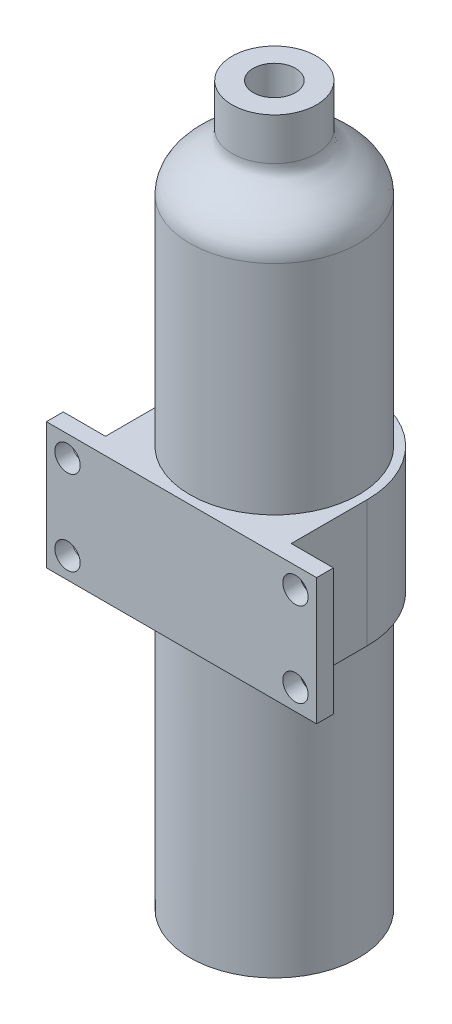
SolidWorks part; units mm, degrees
ref_plane "Alzado" through (0, 0, 0) normal (0, 0, 1) x (1, 0, 0)
ref_plane "Planta" through (0, 0, 0) normal (0, 1, 0) x (1, 0, 0)
ref_plane "Vista lateral" through (0, 0, 0) normal (1, 0, 0) x (0, 0, -1)
sketch "Croquis3" plane through (0, 0, 0) normal (0, 0, 1) x (1, 0, 0)
  line L0 (0, 0) -> (0, 80) construction
  line L1 (0, 80) -> (5, 80) construction
  line L3 (10, 73.2783) -> (10, 0)
  line L4 (10, 0) -> (0, 0)
  line L5 (0, 0) -> (0, 80)
  line L6 (0, 80) -> (5, 80)
  line L7 (10, 42.3793) -> (10, 44.6739) construction
  line L8 (5, 78.1941) -> (5, 79.7862) construction
  spline S0 degree 3 poles (5, 80) (5, 79.0049) (5.6792, 78.3381) (8.8641, 76.2963) (10, 74.7125) (10, 73.2783) knots 0 0 0 0 0.19722 0.426407 1 1 1 1
  point P5 (3.0224, 48.4845)
  point P6 (7.343, 37.9383)
  point P10 (5.5012, 42.0379)
  point P11 (3.5405, 44.5927)
  point P12 (4.4317, 44.1173)
  point P13 (3.0136, 46.7214)
  point P14 (4.0485, 45.5964)
  point P15 (7.2657, 43.5266)
  point P20 (3.1486, 46.2489)
  point P21 (4.8317, 45.644)
  point P22 (3.5453, 46.232)
  point P23 (3.358, 47.5802)
  point P24 (4.7247, 47.3452)
  point P25 (3.2804, 47.6856)
  point P26 (6.905, 46.066)
  point P27 (4.2169, 48.1709)
  point P28 (3.4774, 48.5407)
  point P29 (6.4456, 47.866)
  point P30 (5.6085, 48.4241)
  point P31 (6.7973, 47.7861)
  point P32 (5.4677, 48.5705)
  point P33 (7.0499, 47.7994)
  point P34 (7.0898, 47.693)
  point P35 (5.7735, 48.3445)
  point P36 (10, 43.2783)
  point P37 (7.6514, 47.004)
  dimension "D1" = 80
  dimension "D2" = 10
  dimension "D3" = 5
  dimension "D4" = 3.7257
  dimension "D5" = 5.0661
  dimension "D6" = 1.6555
  dimension "D7" = 2.3486
  dimension "D8" = 1.8779
revolve "Revolución2" add sketch "Croquis3" angle 360 about L5
sketch "Croquis4" plane through (0, 80, 0) normal (0, 1, 0) x (1, 0, 0)
  circle A0 centre (0, 0) radius 5
  dimension "D1" = 10
extrude "Saliente-Extruir1" add sketch "Croquis4" along normal blind 5
sketch "Croquis5" plane through (0, 85, 0) normal (0, 1, 0) x (1, 0, 0)
  circle A0 centre (0, 0) radius 2.5
  dimension "D1" = 5
extrude "Cortar-Extruir1" cut sketch "Croquis5" against normal blind 10
shell "Vaciado2" thickness 2 removed face at (0, 75, 2.5)
ref_plane "Plano1" through (0, 40, 0) normal (0, 1, 0) x (1, 0, 0)
sketch "Croquis6" plane through (0, 40, 0) normal (0, 1, 0) x (1, 0, 0)
  line L0 (-11, 0) -> (-11, -9)
  line L1 (-11, -9) -> (-16, -9)
  line L2 (-16, -9) -> (-16, -11)
  line L3 (-16, -11) -> (16, -11)
  line L4 (16, -11) -> (16, -9)
  line L5 (16, -9) -> (11, -9)
  line L6 (11, -9) -> (11, 0)
  circle A0 centre (0, 0) radius 9
  arc A1 (11, 0) -> (-11, 0) centre (0, 0) ccw
  dimension "D1" = 18
  dimension "D2" = 22
  dimension "D3" = 2
  dimension "D4" = 5
extrude "Saliente-Extruir2" add sketch "Croquis6" along normal mid plane 15
sketch "Croquis7" plane through (0, 0, 9) normal (0, 0, -1) x (-1, 0, 0)
  line L0 (16, 40) -> (-16, 40) construction
  line L1 (16, 47.5) -> (16, 32.5) construction
  line L2 (-16, 47.5) -> (-16, 32.5) construction
  line L3 (-13.5, 35) -> (-13.5, 45) construction
  line L4 (13.5, 35) -> (13.5, 45) construction
  circle A0 centre (-13.5, 45) radius 1.5
  circle A1 centre (-13.5, 35) radius 1.5
  circle A2 centre (13.5, 35) radius 1.5
  circle A3 centre (13.5, 45) radius 1.5
  point P9 (-13.5, 40)
  point P12 (13.5, 40)
  dimension "D4" = 3
  dimension "D1" = 10
  dimension "D2" = 2.5
  dimension "D3" = 2.5
extrude "Cortar-Extruir2" cut sketch "Croquis7" against normal through all
